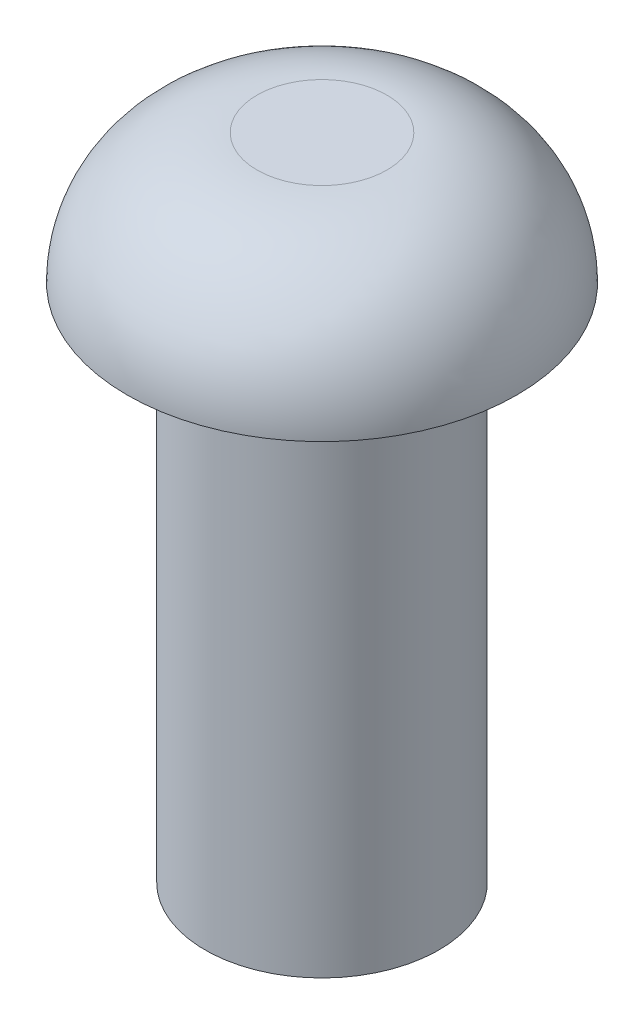
SolidWorks part; units mm, degrees
material "Ti-6Al-2Sn-2Zr-2Mo-2Cr-0.25Si (SS)"
ref_plane "Front Plane" through (0, 0, 0) normal (0, 0, 1) x (1, 0, 0)
ref_plane "Top Plane" through (0, 0, 0) normal (0, 1, 0) x (1, 0, 0)
ref_plane "Right Plane" through (0, 0, 0) normal (1, 0, 0) x (0, 0, -1)
sketch "Sketch1" plane through (0, 0, 0) normal (0, 1, 0) x (1, 0, 0)
  circle A0 centre (0, 0) radius 150
  dimension "D1" = 300
extrude "Boss-Extrude1" add sketch "Sketch1" along normal blind 500
sketch "Sketch2" plane through (0, 0, 0) normal (0, -1, 0) x (1, 0, 0)
  circle A0 centre (0, 0) radius 90
  circle A1 centre (0, 0) radius 150 construction
  circle A2 centre (0, 0) radius 150
  dimension "D1" = 60
extrude "Cut-Extrude1" cut sketch "Sketch2" against normal blind 400
fillet "Fillet1" radius 100 1 edges at (0, 500, 150)
